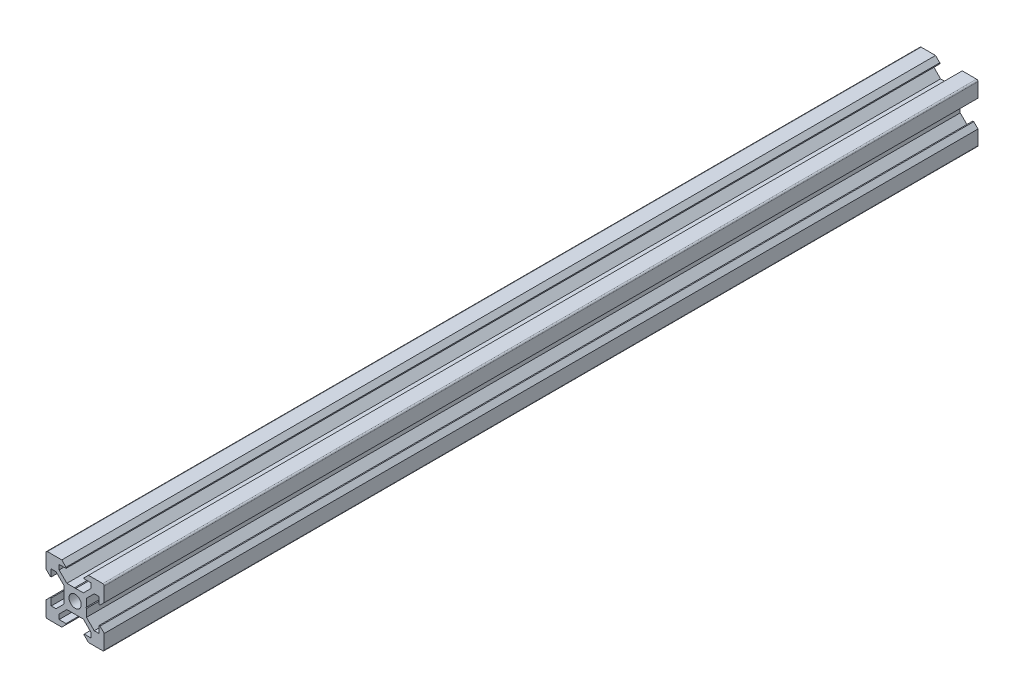
SolidWorks part; units mm, degrees
material "6061-T6 (SS)"
ref_plane "Front Plane" through (0, 0, 0) normal (0, 0, 1) x (1, 0, 0)
ref_plane "Top Plane" through (0, 0, 0) normal (0, 1, 0) x (1, 0, 0)
ref_plane "Right Plane" through (0, 0, 0) normal (1, 0, 0) x (0, 0, -1)
sketch "Sketch1" plane through (0, 0, 0) normal (0, 0, 1) x (1, 0, 0)
  line L1 (9.5, -10) -> (-9.5, -10)
  line L2 (10, -9.5) -> (10, 9.5)
  line L3 (9.5, 10) -> (-9.5, 10)
  line L4 (-10, -9.5) -> (-10, 9.5)
  line L5 (10, -10) -> (-10, 10) construction
  line L6 (10, 10) -> (-10, -10) construction
  circle A0 centre (0, 0) radius 2.1
  arc A1 (-9.5, 10) -> (-10, 9.5) centre (-9.5, 9.5) ccw
  arc A2 (10, 9.5) -> (9.5, 10) centre (9.5, 9.5) ccw
  arc A3 (9.5, -10) -> (10, -9.5) centre (9.5, -9.5) ccw
  arc A4 (-9.5, -10) -> (-10, -9.5) centre (-9.5, -9.5) cw
  point P0 (0, 0)
  line B0 (0, 0) -> (0, 10) construction
  line B1 (0, 3.69) -> (-0.21, 3.9)
  line B2 (-0.21, 3.9) -> (-2.8393, 3.9)
  line B3 (-2.8393, 3.9) -> (-5.5, 6.5607)
  line B4 (-5.5, 6.5607) -> (-5.5, 8.2)
  line B5 (-5.5, 8.2) -> (-3.125, 8.2)
  line B6 (-3.125, 8.2) -> (-3.125, 8.545)
  line B7 (-3.125, 8.545) -> (-4.58, 10)
  line B8 (-4.58, 10) -> (4.58, 10)
  line B9 (0, 0) -> (-5.9132, 5.9132) construction
  line B10 (3.125, 8.545) -> (4.58, 10)
  line B11 (3.125, 8.2) -> (3.125, 8.545)
  line B12 (5.5, 8.2) -> (3.125, 8.2)
  line B13 (5.5, 6.5607) -> (5.5, 8.2)
  line B14 (2.8393, 3.9) -> (5.5, 6.5607)
  line B15 (0.21, 3.9) -> (2.8393, 3.9)
  line B16 (0, 3.69) -> (0.21, 3.9)
  line B17 (0, 0) -> (-10, 0) construction
  line B18 (-3.69, 0) -> (-3.9, -0.21)
  line B19 (-3.9, -0.21) -> (-3.9, -2.8393)
  line B20 (-3.9, -2.8393) -> (-6.5607, -5.5)
  line B21 (-6.5607, -5.5) -> (-8.2, -5.5)
  line B22 (-8.2, -5.5) -> (-8.2, -3.125)
  line B23 (-8.2, -3.125) -> (-8.545, -3.125)
  line B24 (-8.545, -3.125) -> (-10, -4.58)
  line B25 (-10, -4.58) -> (-10, 4.58)
  line B26 (0, 0) -> (-5.9132, -5.9132) construction
  line B27 (-8.545, 3.125) -> (-10, 4.58)
  line B28 (-8.2, 3.125) -> (-8.545, 3.125)
  line B29 (-8.2, 5.5) -> (-8.2, 3.125)
  line B30 (-6.5607, 5.5) -> (-8.2, 5.5)
  line B31 (-3.9, 2.8393) -> (-6.5607, 5.5)
  line B32 (-3.9, 0.21) -> (-3.9, 2.8393)
  line B33 (-3.69, 0) -> (-3.9, 0.21)
  line B34 (0, 0) -> (0, -10) construction
  line B35 (0, -3.69) -> (0.21, -3.9)
  line B36 (0.21, -3.9) -> (2.8393, -3.9)
  line B37 (2.8393, -3.9) -> (5.5, -6.5607)
  line B38 (5.5, -6.5607) -> (5.5, -8.2)
  line B39 (5.5, -8.2) -> (3.125, -8.2)
  line B40 (3.125, -8.2) -> (3.125, -8.545)
  line B41 (3.125, -8.545) -> (4.58, -10)
  line B42 (4.58, -10) -> (-4.58, -10)
  line B43 (0, 0) -> (5.9132, -5.9132) construction
  line B44 (-3.125, -8.545) -> (-4.58, -10)
  line B45 (-3.125, -8.2) -> (-3.125, -8.545)
  line B46 (-5.5, -8.2) -> (-3.125, -8.2)
  line B47 (-5.5, -6.5607) -> (-5.5, -8.2)
  line B48 (-2.8393, -3.9) -> (-5.5, -6.5607)
  line B49 (-0.21, -3.9) -> (-2.8393, -3.9)
  line B50 (0, -3.69) -> (-0.21, -3.9)
  line B51 (0, 0) -> (10, 0) construction
  line B52 (3.69, 0) -> (3.9, 0.21)
  line B53 (3.9, 0.21) -> (3.9, 2.8393)
  line B54 (3.9, 2.8393) -> (6.5607, 5.5)
  line B55 (6.5607, 5.5) -> (8.2, 5.5)
  line B56 (8.2, 5.5) -> (8.2, 3.125)
  line B57 (8.2, 3.125) -> (8.545, 3.125)
  line B58 (8.545, 3.125) -> (10, 4.58)
  line B59 (10, 4.58) -> (10, -4.58)
  line B60 (0, 0) -> (5.9132, 5.9132) construction
  line B61 (8.545, -3.125) -> (10, -4.58)
  line B62 (8.2, -3.125) -> (8.545, -3.125)
  line B63 (8.2, -5.5) -> (8.2, -3.125)
  line B64 (6.5607, -5.5) -> (8.2, -5.5)
  line B65 (3.9, -2.8393) -> (6.5607, -5.5)
  line B66 (3.9, -0.21) -> (3.9, -2.8393)
  line B67 (3.69, 0) -> (3.9, -0.21)
  dimension "D1" = 4.2
  dimension "D3" = 0.5
  dimension "D2" = 20
sketch_block_instance "V Slot 1-4"
sketch_block "V Slot 1" parameters "D1"=10, "D2"=11, "D3"=4.3, "D4"=1.8, "D5"=0.21, "D6"=45, "D7"=9.16, "D8"=1.5, "D9"=6.25
sketch_block_instance "V Slot 1-5"
sketch_block_instance "V Slot 1-6"
sketch_block_instance "V Slot 1-7"
extrude "Boss-Extrude1" add sketch "Sketch1" along normal blind 300 contours B67 B52 B53 B54 B55 B56 B57 B58 L2 A2 L3 B10 B11 B12 B13 B14 B15 B16 B1 B2 B3 B4 B5 B6 B7 A1 L4 B27 B28 B29 B30 B31 B32 B33 B18 B19 B20 B21 B22 B23 B24 A4 L1 B44 B45 B46 B47 B48 B49 region at (7.04, -9.7172, 0)
